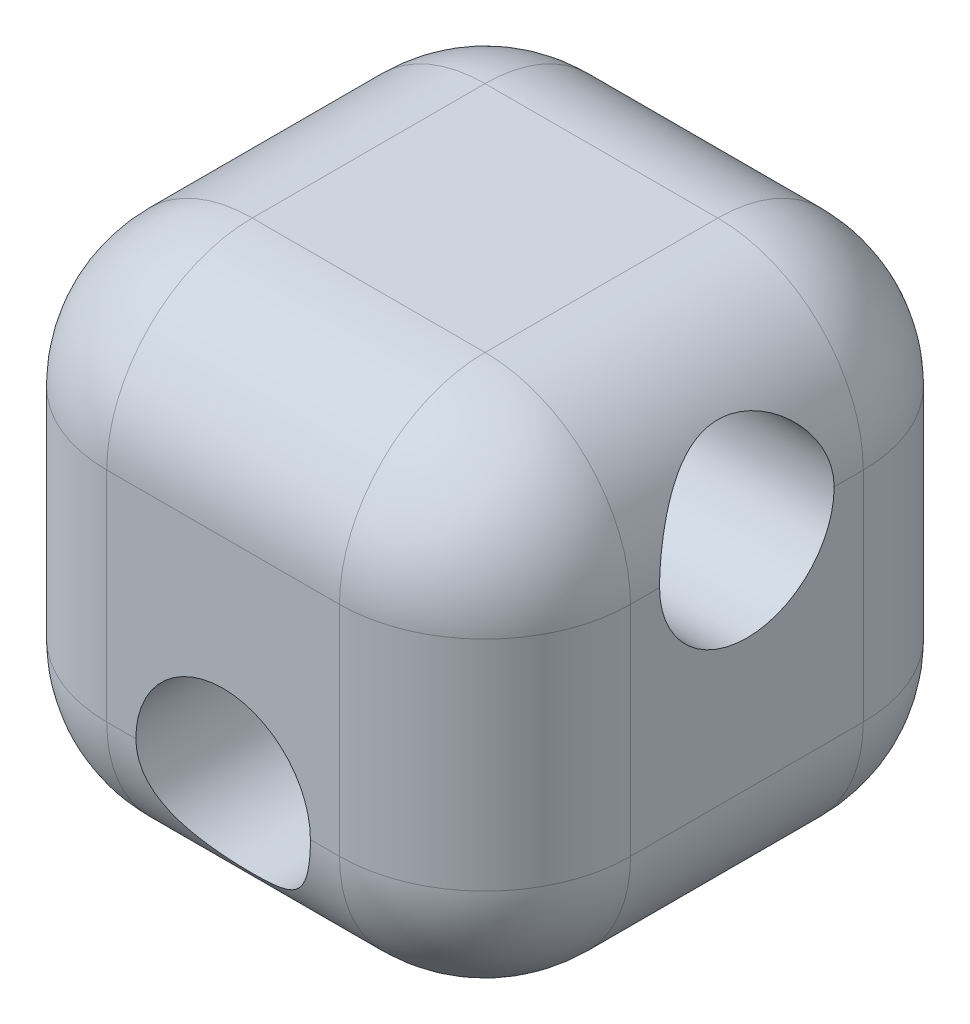
SolidWorks part; units mm, degrees
ref_plane "Front Plane" through (0, 0, 0) normal (0, 0, 1) x (1, 0, 0)
ref_plane "Top Plane" through (0, 0, 0) normal (0, 1, 0) x (1, 0, 0)
ref_plane "Right Plane" through (0, 0, 0) normal (1, 0, 0) x (0, 0, -1)
sketch "Sketch1" plane through (0, 0, 0) normal (0, 1, 0) x (1, 0, 0)
  line L1 (-18, 18) -> (18, 18)
  line L2 (-18, 18) -> (-18, -18)
  line L3 (-18, -18) -> (18, -18)
  line L4 (18, 18) -> (18, -18)
  line L5 (-18, 18) -> (18, -18) construction
  line L6 (-18, -18) -> (18, 18) construction
  point P0 (0, 0)
  dimension "D1" = 36
  dimension "D2" = 36
extrude "Boss-Extrude1" add sketch "Sketch1" along normal blind 35
sketch "Sketch2" plane through (0, 0, 18) normal (0, 0, 1) x (1, 0, 0)
  line L1 (-18, 0) -> (18, 0) construction
  line L2 (0, 35) -> (0, 0) construction
  line L3 (-18, 35) -> (18, 35) construction
  circle A0 centre (0, 10) radius 6
  dimension "D1" = 12
  dimension "D3" = 10
extrude "Cut-Extrude1" cut sketch "Sketch2" against normal through all
sketch "Sketch3" plane through (18, 0, 0) normal (1, 0, 0) x (0, 0, -1)
  line L1 (-18, 35) -> (18, 35) construction
  line L2 (0, 35) -> (0, 0) construction
  line L3 (18, 35) -> (-18, 35) construction
  circle A0 centre (0, 25) radius 6
  dimension "D3" = 12
  dimension "D2" = 10
extrude "Cut-Extrude2" cut sketch "Sketch3" against normal through all
fillet "Fillet1" radius 10 4 edges at (18, 17.5, -18) (-18, 17.5, -18) (18, 17.5, 18) (-18, 17.5, 18)
fillet "Fillet2" radius 10 16 edges at (15.0711, 0, -15.0711) (18, 0, 0) (15.0711, 0, 15.0711) (0, 0, 18) (-15.0711, 0, 15.0711) (-18, 0, 0) (-15.0711, 0, -15.0711) (18, 35, 0) (15.0711, 35, 15.0711) (0, 35, 18) (-15.0711, 35, 15.0711) (-18, 35, 0) (-15.0711, 35, -15.0711) (0, 35, -18) (0, 0, -18) (15.0711, 35, -15.0711)
